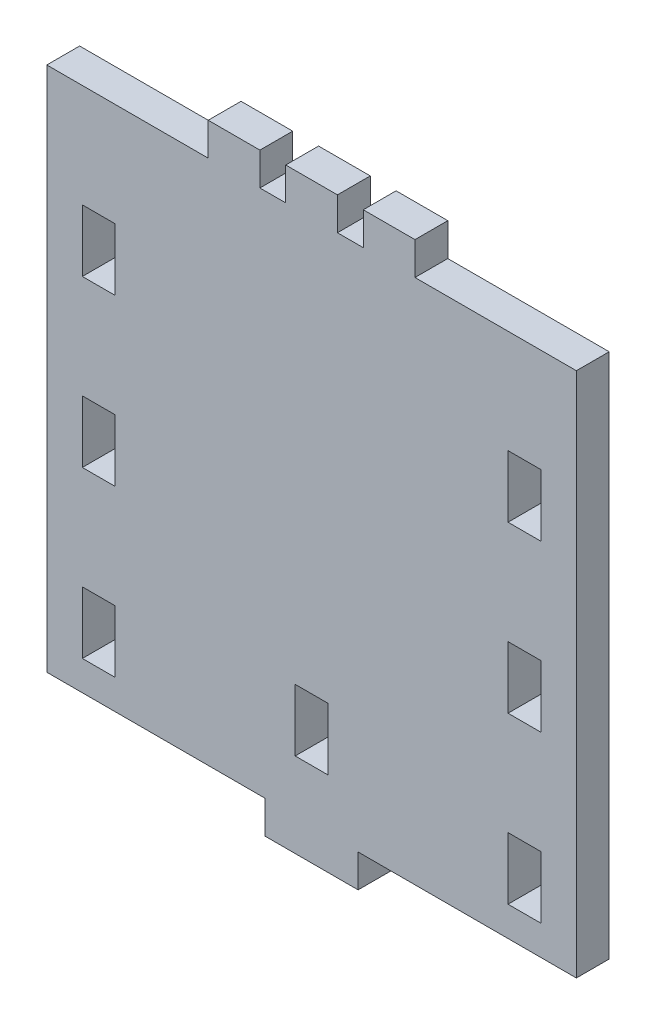
SolidWorks part; units mm, degrees
ref_plane "Front Plane" through (0, 0, 0) normal (0, 0, 1) x (1, 0, 0)
ref_plane "Top Plane" through (0, 0, 0) normal (0, 1, 0) x (1, 0, 0)
ref_plane "Right Plane" through (0, 0, 0) normal (1, 0, 0) x (0, 0, -1)
sketch "Sketch1" plane through (0, 0, 0) normal (0, 0, 1) x (1, 0, 0)
  line L0 (0, 0) -> (-21.1125, 0)
  line L1 (-21.1125, 0) -> (-21.1125, -3.175)
  line L2 (-21.1125, -3.175) -> (-30.1125, -3.175)
  line L3 (-30.1125, -3.175) -> (-30.1125, 0)
  line L4 (-30.1125, 0) -> (-51.225, 0)
  line L5 (-51.225, 0) -> (-51.225, 50.875)
  line L6 (-51.225, 50.875) -> (-35.6125, 50.875)
  line L7 (-35.6125, 50.875) -> (-35.6125, 54.05)
  line L8 (-35.6125, 54.05) -> (-30.6125, 54.05)
  line L9 (-30.6125, 54.05) -> (-30.6125, 50.875)
  line L10 (-30.6125, 50.875) -> (-28.1125, 50.875)
  line L11 (-28.1125, 50.875) -> (-28.1125, 54.05)
  line L12 (-28.1125, 54.05) -> (-23.1125, 54.05)
  line L13 (-23.1125, 54.05) -> (-23.1125, 50.875)
  line L14 (-23.1125, 50.875) -> (-20.6125, 50.875)
  line L15 (-20.6125, 50.875) -> (-20.6125, 54.05)
  line L16 (-20.6125, 54.05) -> (-15.6125, 54.05)
  line L17 (-15.6125, 54.05) -> (-15.6125, 50.875)
  line L18 (-15.6125, 50.875) -> (0, 50.875)
  line L19 (0, 50.875) -> (0, 0)
  line L22 (-3.4375, 8.875) -> (-3.4375, 2.875)
  line L23 (-3.4375, 8.875) -> (-6.6125, 8.875)
  line L24 (-6.6125, 8.875) -> (-6.6125, 2.875)
  line L25 (-6.6125, 2.875) -> (-3.4375, 2.875)
  line L26 (0, 25.4375) -> (-5.025, 25.4375) construction
  line L27 (-5.025, 8.875) -> (-5.025, 18.875) construction
  line L28 (-5.025, 18.875) -> (-3.4375, 18.875)
  line L29 (-3.4375, 18.875) -> (-3.4375, 24.875)
  line L30 (-3.4375, 24.875) -> (-6.6125, 24.875)
  line L31 (-6.6125, 24.875) -> (-6.6125, 18.875)
  line L32 (-6.6125, 18.875) -> (-5.025, 18.875)
  line L33 (-5.025, 24.875) -> (-5.025, 34.875) construction
  line L34 (-5.025, 34.875) -> (-3.4375, 34.875)
  line L35 (-3.4375, 34.875) -> (-3.4375, 40.875)
  line L36 (-3.4375, 40.875) -> (-6.6125, 40.875)
  line L37 (-6.6125, 40.875) -> (-6.6125, 34.875)
  line L38 (-6.6125, 34.875) -> (-5.025, 34.875)
  line L43 (-25.6125, -3.175) -> (-25.6125, 5) construction
  line L44 (-5.025, 40.875) -> (-5.025, 50.875) construction
  line L45 (-46.2, 24.875) -> (-46.2, 34.875) construction
  line L46 (-46.2, 8.875) -> (-46.2, 18.875) construction
  line L47 (-44.6125, 34.875) -> (-46.2, 34.875)
  line L48 (-44.6125, 40.875) -> (-44.6125, 34.875)
  line L49 (-47.7875, 40.875) -> (-44.6125, 40.875)
  line L50 (-47.7875, 34.875) -> (-47.7875, 40.875)
  line L51 (-46.2, 34.875) -> (-47.7875, 34.875)
  line L52 (-44.6125, 18.875) -> (-46.2, 18.875)
  line L53 (-44.6125, 24.875) -> (-44.6125, 18.875)
  line L54 (-47.7875, 24.875) -> (-44.6125, 24.875)
  line L55 (-47.7875, 18.875) -> (-47.7875, 24.875)
  line L56 (-46.2, 18.875) -> (-47.7875, 18.875)
  line L57 (-44.6125, 2.875) -> (-47.7875, 2.875)
  line L58 (-44.6125, 8.875) -> (-44.6125, 2.875)
  line L59 (-47.7875, 8.875) -> (-44.6125, 8.875)
  line L60 (-47.7875, 8.875) -> (-47.7875, 2.875)
  line L61 (-5, 25.4375) -> (-25.6701, 25.4375) construction
  line L62 (-24.025, 5) -> (-25.6125, 5)
  line L63 (-24.025, 11) -> (-24.025, 5)
  line L64 (-27.2, 11) -> (-24.025, 11)
  line L65 (-27.2, 5) -> (-27.2, 11)
  line L66 (-25.6125, 5) -> (-27.2, 5)
  dimension "D1" = 3.175
  dimension "D2" = 3.4375
  dimension "D3" = 9
  dimension "D4" = 5
  dimension "D5" = 5
  dimension "D6" = 2.875
  dimension "D7" = 38
  dimension "D8" = 3.175
  dimension "D9" = 6
  dimension "D10" = 10
  dimension "D11" = 6
  dimension "D12" = 3.175
extrude "Boss-Extrude1" add sketch "Sketch1" along normal mid plane 3.175
